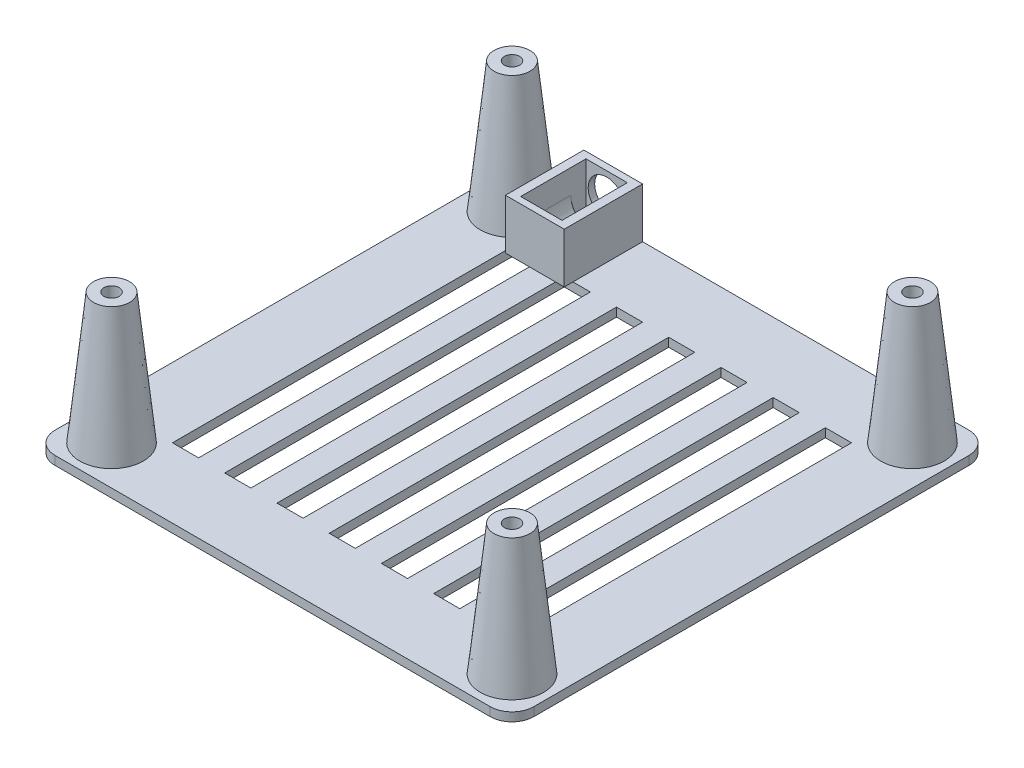
SolidWorks part; units mm, degrees
ref_plane "前视基准面" through (0, 0, 0) normal (0, 0, 1) x (1, 0, 0)
ref_plane "上视基准面" through (0, 0, 0) normal (0, 1, 0) x (1, 0, 0)
ref_plane "右视基准面" through (0, 0, 0) normal (1, 0, 0) x (0, 0, -1)
sketch "草图1" plane through (0, 0, 0) normal (0, 1, 0) x (1, 0, 0)
  line L0 (-74.6392, 0) -> (70.2469, 0) construction
  line L1 (-55, 55) -> (55, 55)
  line L2 (-55, 55) -> (-55, -55)
  line L3 (-55, -55) -> (55, -55)
  line L4 (55, 55) -> (55, -55)
  line L5 (-55, 55) -> (55, -55) construction
  line L6 (-55, -55) -> (55, 55) construction
  line L7 (0, 87.0647) -> (0, -86.9016) construction
  circle A0 centre (-46, -46) radius 1.75
  circle A1 centre (-46, -46) radius 7.5
  circle A2 centre (46, -46) radius 1.75
  circle A3 centre (46, -46) radius 7.5
  circle A4 centre (46, 46) radius 1.75
  circle A5 centre (46, 46) radius 7.5
  circle A6 centre (-46, 46) radius 7.5
  circle A7 centre (-46, 46) radius 1.75
  circle A8 centre (-46, -46) radius 3.5
  circle A9 centre (-46, 46) radius 3.5
  circle A10 centre (46, -46) radius 3.5
  circle A11 centre (46, 46) radius 3.5
  point P0 (0, 0)
  dimension "D5" = 3.5
  dimension "D6" = 15
  dimension "D7" = 7
  dimension "D1" = 110
  dimension "D2" = 110
  dimension "D3" = 9
  dimension "D4" = 9
extrude "凸台-拉伸1" add sketch "草图1" along normal blind 2 contours L4 L1 L2 L3 A3 A1 A5 A6 | A3 A2 | A5 A4 | A6 A7 | A1 A8 | A8 A0 | A2 | A4 | A0 | A7 region at (0, 0, 0) region at (-53.2879, 0, 46) region at (46, 0, 46) region at (38.7121, 0, 46) region at (46, 0, -46) region at (38.7121, 0, -46) region at (-53.2879, 0, -46) region at (-49.401, 0, 46)
extrude "凸台-拉伸2" add sketch "草图1<3>" along normal blind 32 draft 6 contours A6 | A1 | A3 | A5
sketch "草图1<3>" plane through (0, 0, 0) normal (0, 1, 0) x (1, 0, 0) same geometry as "草图1"
extrude "切除-拉伸1" cut sketch "草图1<4>" along normal up to next (32 mm away) contours A7 | A0 | A2 | A4 region at (-46, 0, 46) region at (46, 0, 46) region at (46, 0, -46) region at (-46, 0, -46)
sketch "草图1<4>" plane through (0, 0, 0) normal (0, 1, 0) x (1, 0, 0) same geometry as "草图1"
fillet "圆角1" radius 5 4 edges at (-55, 1, 55) (55, 1, 55) (55, 1, -55) (-55, 1, -55)
sketch "草图2" plane through (0, 0, 0) normal (0, -1, 0) x (1, 0, 0)
  line L0 (-33, -39) -> (-33, 39)
  line L1 (-39, -39) -> (39, -39)
  line L2 (-39, -39) -> (-39, 39)
  line L3 (-39, 39) -> (39, 39)
  line L4 (39, -39) -> (39, 39)
  line L5 (-39, -39) -> (39, 39) construction
  line L6 (-39, 39) -> (39, -39) construction
  line L7 (-27, -39) -> (-27, 39)
  line L8 (-15, -39) -> (-15, 39)
  line L9 (-9, -39) -> (-9, 39)
  line L10 (-33, -39) -> (-33, 39)
  line L11 (-21, -39) -> (-21, 39)
  line L12 (-3, -39) -> (-3, 39)
  line L13 (3, -39) -> (3, 39)
  line L14 (9, -39) -> (9, 39)
  line L15 (15, -39) -> (15, 39)
  line L16 (21, -39) -> (21, 39)
  line L17 (27, -39) -> (27, 39)
  line L18 (33, -39) -> (33, 39)
  line L19 (39, -39) -> (39, 39)
  point P0 (0, 0)
  dimension "D1" = 78
  dimension "D2" = 78
  dimension "D3" = 6
  dimension "D4" = 6
  dimension "D5" = 6
  dimension "D6" = 6
  dimension "D7" = 6
  dimension "D8" = 6
  dimension "D9" = 6
  dimension "D10" = 6
  dimension "D11" = 6
  dimension "D12" = 6
  dimension "D13" = 6
  dimension "D14" = 6
  dimension "D15" = 6
extrude "切除-拉伸2" cut sketch "草图2" against normal through all contours L3 L2 L1 L0 | L1 L11 L3 L7 | L1 L9 L3 L8 | L1 L13 L3 L12 | L1 L15 L3 L14 | L1 L17 L3 L16 | L1 L19 L3 L18 region at (-36, 0, 0) region at (-24, 0, 0) region at (-12, 0, 0) region at (0, 0, 0) region at (12, 0, 0) region at (24, 0, 0) region at (36, 0, 0)
sketch "草图3" plane through (0, 0, -55) normal (0, 0, -1) x (-1, 0, 0)
  line L0 (50, 2) -> (-50, 2) construction
  line L1 (36.5, 2) -> (27, 2)
  line L2 (55, 2) -> (55, 0) construction
  line L3 (27, 2) -> (27, 13.5)
  line L4 (27, 13.5) -> (36.5, 13.5)
  line L5 (36.5, 13.5) -> (36.5, 2)
  line L6 (25, 2) -> (25, 13.5)
  line L8 (38.5, 13.5) -> (38.5, 2)
  line L9 (27, 2) -> (25, 2)
  line L10 (36.5, 2) -> (38.5, 2)
  line L11 (27, 13.5) -> (25, 13.5)
  line L12 (25, 0) -> (25, 15.5) construction
  line L13 (38.5, 15.5) -> (38.5, 0) construction
  line L14 (38.5, 0) -> (25, 0) construction
  line L15 (36.5, 13.5) -> (38.5, 13.5)
  line L16 (25, 15.5) -> (38.5, 15.5) construction
  circle A0 centre (31.75, 8) radius 4.25
  arc A1 (27, 8) -> (36.5, 8) centre (31.75, 8) ccw
  point P0 (36.5, 2)
  line M1 (50, 2) -> (-50, 2)
  dimension "D6" = 9.5
  dimension "D7" = 8.5
  dimension "D1" = 18.5
  dimension "D3" = 9.5
  dimension "D4" = 11.5
  dimension "D5" = 5.5
  dimension "D2" = 2
extrude "凸台-拉伸6" add sketch "草图3" against normal blind 18 separate body contours L3 L11 L6 M1 | A1 L5 L4 L3 | L15 L5 L8 M1 | A1 L3 L5 M1 | A1 A0 | A0 region at (-31.75, 2.1124, -55) region at (-37.5, 7.75, -55) region at (-26, 7.75, -55) region at (-31.75, 3.3898, -55) region at (-31.75, 8, -55)
extrude "切除-拉伸4" cut sketch "草图3<5>" against normal blind 3.5 from offset 1.5 contours L3 A1 L5 L4 A0 | A1 L3 L5 M1 region at (-31.75, 2.1124, -55) region at (-31.75, 3.3898, -55) offset against normal yes
sketch "草图3<5>" plane through (0, 0, -55) normal (0, 0, -1) x (-1, 0, 0) same geometry as "草图3"
extrude "切除-拉伸5" cut sketch "草图3<6>" against normal blind 15 from offset 1.5 contours L3 A1 L5 L4 A0 region at (-31.75, 3.3898, -55) offset against normal yes
sketch "草图3<6>" plane through (0, 0, -55) normal (0, 0, -1) x (-1, 0, 0) same geometry as "草图3"
extrude "切除-拉伸6" cut sketch "草图1<5>" along normal blind 25 contours A8 A0 | A10 | A9 | A11 region at (-49.401, 0, 46)
sketch "草图1<5>" plane through (0, 0, 0) normal (0, 1, 0) x (1, 0, 0) same geometry as "草图1"
extrude "切除-拉伸7" cut sketch "草图3<7>" against normal blind 16.5 contours A0 region at (-31.75, 8, -55)
sketch "草图3<7>" plane through (0, 0, -55) normal (0, 0, -1) x (-1, 0, 0) same geometry as "草图3"
